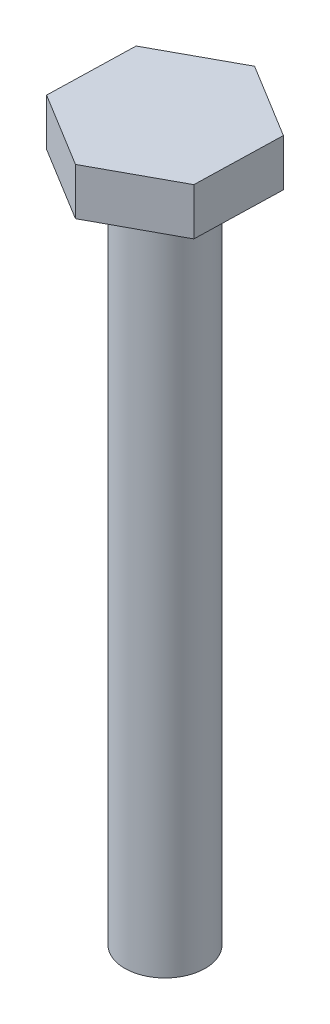
SolidWorks part; units mm, degrees
ref_plane "Front Plane" through (0, 0, 0) normal (0, 0, 1) x (1, 0, 0)
ref_plane "Top Plane" through (0, 0, 0) normal (0, 1, 0) x (1, 0, 0)
ref_plane "Right Plane" through (0, 0, 0) normal (1, 0, 0) x (0, 0, -1)
sketch "Sketch1" plane through (0, 0, 0) normal (0, 1, 0) x (1, 0, 0)
  line L1 (5.5434, -3.3943) -> (5.7112, 3.1035)
  line L2 (5.7112, 3.1035) -> (0.1679, 6.4978)
  line L3 (0.1679, 6.4978) -> (-5.5434, 3.3943)
  line L4 (-5.5434, 3.3943) -> (-5.7112, -3.1035)
  line L5 (-5.7112, -3.1035) -> (-0.1679, -6.4978)
  line L6 (-0.1679, -6.4978) -> (5.5434, -3.3943)
  circle A0 centre (0, 0) radius 5.6292 construction
extrude "Boss-Extrude1" add sketch "Sketch1" along normal blind 3.5
sketch "Sketch2" plane through (0, 0, 0) normal (0, -1, 0) x (1, 0, 0)
  circle A0 centre (0, 0) radius 3
extrude "Boss-Extrude2" add sketch "Sketch2" along normal blind 50
move or copy body "Body-Move/Copy1" [suppressed] bodies to move or copy 102
